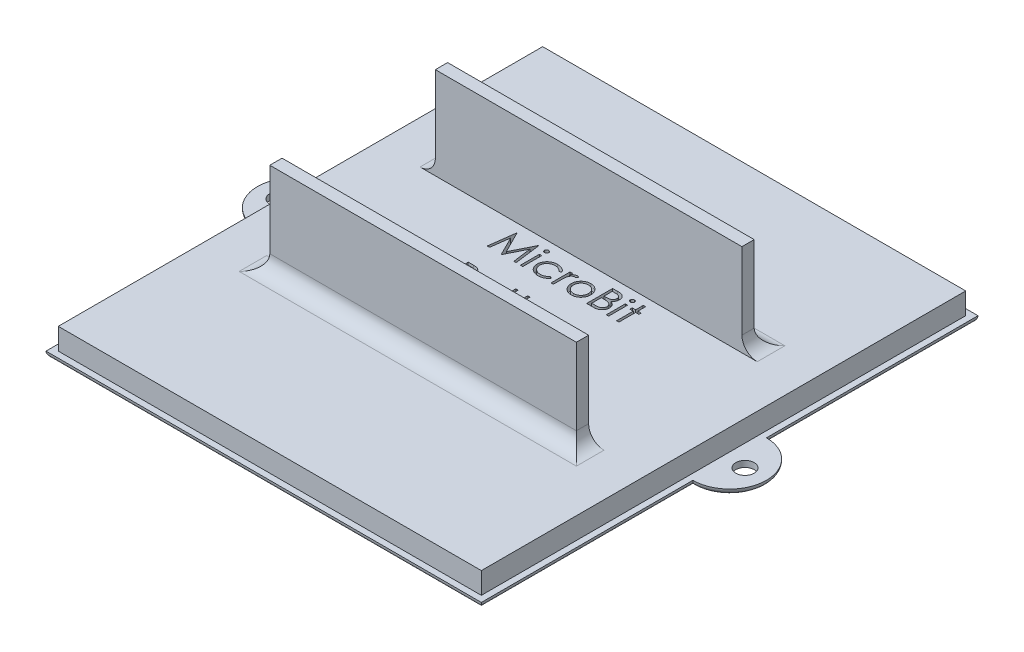
SolidWorks part; units mm, degrees
other "DetailItem2"
other "Markup1"
sketch "Sketch11" plane through (-41.5, 7, -35.5) normal (0, 1, 0) x (1, 0, 0)
sketch "Sketch12" plane through (-41.5, 7, -35.5) normal (0, 1, 0) x (1, 0, 0)
sketch "Sketch13" plane through (-41.5, 7, -35.5) normal (0, 1, 0) x (1, 0, 0)
sketch "Sketch15" plane through (-41.5, 7, -35.5) normal (0, 1, 0) x (1, 0, 0)
sketch "Sketch16" plane through (-41.5, 7, -35.5) normal (0, 1, 0) x (1, 0, 0)
sketch "Sketch17" plane through (-41.5, 7, -35.5) normal (0, 1, 0) x (1, 0, 0)
sketch "Sketch18" plane through (-41.5, 7, -35.5) normal (0, 1, 0) x (1, 0, 0)
sketch "Sketch19" plane through (-41.5, 7, -35.5) normal (0, 1, 0) x (1, 0, 0)
sketch "Sketch20" plane through (-41.5, 12, -35.5) normal (0, 1, 0) x (1, 0, 0)
sketch "Sketch21" plane through (-41.5, 12, -35.5) normal (0, 1, 0) x (1, 0, 0)
sketch "Sketch22" plane through (-41.5, 12, -35.5) normal (0, 1, 0) x (1, 0, 0)
sketch "Sketch31" plane through (-41.5, 25.5, -40.5) normal (0, 1, 0) x (1, 0, 0)
sketch "Sketch32" plane through (-41.5, 25.5, -40.5) normal (0, 1, 0) x (1, 0, 0)
sketch "Sketch38" plane through (-41.5, 25.5, -40.5) normal (0, 1, 0) x (1, 0, 0)
sketch "Sketch39" plane through (-41.5, 25.5, -40.5) normal (0, 1, 0) x (1, 0, 0)
sketch "Sketch40" plane through (-41.5, 25.5, -40.5) normal (0, 1, 0) x (1, 0, 0)
sketch "Sketch41" plane through (-41.5, 19.5, -40.5) normal (0, 1, 0) x (1, 0, 0)
sketch "Sketch44" plane through (-41.5, 19.5, -40.5) normal (0, 1, 0) x (1, 0, 0)
sketch "Sketch45" plane through (-41.5, 19.5, -40.5) normal (0, 1, 0) x (1, 0, 0)
sketch "Sketch47" plane through (-41.5, 19.5, -40.5) normal (0, 1, 0) x (1, 0, 0)
ref_plane "Front Plane" through (0, 0, 0) normal (0, 0, 1) x (1, 0, 0)
ref_plane "Top Plane" through (0, 0, 0) normal (0, 1, 0) x (1, 0, 0)
ref_plane "Right Plane" through (0, 0, 0) normal (1, 0, 0) x (0, 0, -1)
sketch "Sketch1" plane through (0, 0, 0) normal (0, 1, 0) x (1, 0, 0)
  line L1 (-35.5, -40.5) -> (35.5, -40.5)
  line L2 (-35.5, -40.5) -> (-35.5, 40.5)
  line L3 (-35.5, 40.5) -> (35.5, 40.5)
  line L4 (35.5, -40.5) -> (35.5, 40.5)
  line L5 (-35.5, -40.5) -> (35.5, 40.5) construction
  line L6 (-35.5, 40.5) -> (35.5, -40.5) construction
  point P0 (0, 0)
  dimension "D1" = 81
  dimension "D2" = 71
extrude "Boss-Extrude1" add sketch "Sketch1" along normal blind 4.5
sketch "text" plane through (0, 4.5, 0) normal (0, 1, 0) x (1, 0, 0)
  line L0 (-35.4043, 6.8177) -> (35.5957, 6.8177) construction
  text T0 "MicroBit\r\nBattery \r\nHolder" font "Century Gothic" height in points 16
extrude "Cut-Extrude1" cut sketch "text" against normal blind 1
sketch "Sketch4" plane through (0, 4.5, 0) normal (0, 1, 0) x (1, 0, 0)
  line L0 (-35.5, 40.5) -> (-35.5, -40.5) construction
  line L1 (-35.5, 6) -> (-35.5, -6)
  arc A0 (-35.5, 6) -> (-35.5, -6) centre (-35.5, 0) ccw
  dimension "D1" = 6
extrude "Boss-Extrude3" add sketch "Sketch4" against normal up to surface (4.5 mm away) up to face at (0, 0, 0)
sketch "Sketch5" plane through (0, 4.5, 0) normal (0, 1, 0) x (1, 0, 0)
  line L0 (-35.5, 40.5) -> (-35.5, 6) construction
  circle A0 centre (-38, 0) radius 1.5
  dimension "D1" = 3
  dimension "D2" = 2.5
extrude "Cut-Extrude2" cut sketch "Sketch5" against normal up to surface (4.5 mm away) up to face at (-12.8333, 0, 0)
mirror "Mirror3" about plane through (0, 0, 0) normal (1, 0, 0) of "Boss-Extrude3", "Cut-Extrude2"
sketch "Sketch9" plane through (0, 4.5, 0) normal (0, 1, 0) x (1, 0, 0)
  line L1 (-25, 14.5) -> (25, 14.5)
  line L2 (-25, 14.5) -> (-25, 12.5)
  line L3 (-25, 12.5) -> (25, 12.5)
  line L4 (25, 14.5) -> (25, 12.5)
  point P4 (0, 14.5)
  dimension "D1" = 50
  dimension "D2" = 2
  dimension "D3" = 12.5
extrude "top track" add sketch "Sketch9" along normal blind 15 contours L2 L1 L4 L3
fillet "Fillet1" radius 2.5 3 edges at (25, 4.5, -13.5) (0, 4.5, -14.5) (-25, 4.5, -13.5)
mirror "Mirror4" about plane through (0, 0, 0) normal (0, 0, 1) of "top track", "Fillet1"
sketch "Sketch46" plane through (0, 4.5, 0) normal (0, 1, 0) x (1, 0, 0)
  line L0 (35.5, 40.5) -> (-35.5, 40.5) construction
  line L1 (-34.5, -39.5) -> (34.5, -39.5)
  line L2 (-34.5, -39.5) -> (-34.5, 39.5)
  line L3 (-34.5, 39.5) -> (34.5, 39.5)
  line L4 (34.5, -39.5) -> (34.5, 39.5)
  line L5 (-34.5, -39.5) -> (34.5, 39.5) construction
  line L6 (-34.5, 39.5) -> (34.5, -39.5) construction
  line L7 (35.5, 6) -> (35.5, 40.5) construction
  line L8 (-44.5, 49.5) -> (44.5, 49.5)
  line L9 (44.5, -49.5) -> (44.5, 49.5)
  line L10 (-44.5, -49.5) -> (44.5, -49.5)
  line L11 (-44.5, -49.5) -> (-44.5, 49.5)
  point P0 (0, 0)
  dimension "D1" = 1
  dimension "D2" = 1
  dimension "D3" = 10
extrude "Cut-Extrude3" cut sketch "Sketch46" against normal offset from surface (3.5 mm away) 1 up to face at (38, 0, -1.5)
fillet "Fillet2" radius 1 8 edges at (-35.5, 0, 23.25) (-41.5, 0, 0) (-35.5, 0, -23.25) (0, 0, -40.5) (35.5, 0, -23.25) (41.5, 0, 0) (0, 0, 40.5) (35.5, 0, 23.25)
equation "\"Screw_Diameter\"=3"
